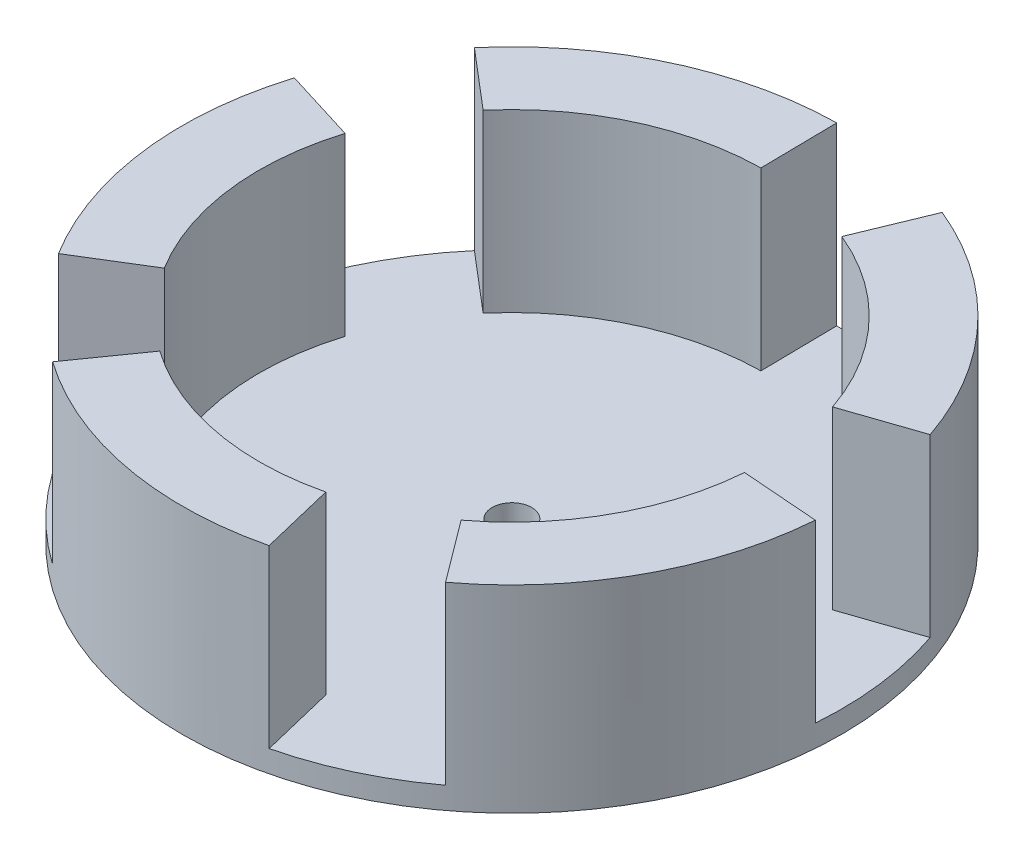
SolidWorks part; units mm, degrees
ref_plane "Front Plane" through (0, 0, 0) normal (0, 0, 1) x (1, 0, 0)
ref_plane "Top Plane" through (0, 0, 0) normal (0, 1, 0) x (1, 0, 0)
ref_plane "Right Plane" through (0, 0, 0) normal (1, 0, 0) x (0, 0, -1)
sketch "Sketch3" plane through (0, 0, 0) normal (0, 1, 0) x (1, 0, 0)
  circle A0 centre (0, 0) radius 30
  dimension "D2" = 60
extrude "Boss-Extrude3" add sketch "Sketch3" along normal blind 2
sketch "Sketch4" plane through (0, 2, 0) normal (0, 1, 0) x (1, 0, 0)
  line L0 (0, 0) -> (-17.5189, 14.9027) construction
  line L1 (0, 0) -> (8.7596, 21.2666) construction
  line L2 (0, 0) -> (21.7702, 7.4201) construction
  line L3 (0, 0) -> (22.9326, -1.7592) construction
  line L4 (0, 0) -> (13.7843, -18.4118) construction
  line L5 (0, 0) -> (5.4135, -22.3538) construction
  line L6 (0, 0) -> (-13.251, -18.7992) construction
  line L7 (0, 0) -> (-19.5869, -12.0563) construction
  line L8 (0, 0) -> (-21.9739, 6.7932) construction
  line L9 (0, 0) -> (-0.3296, 22.9976) construction
  line L10 (-17.5189, 14.9027) -> (-0.3296, 22.9976) construction
  line L11 (-0.3296, 22.9976) -> (8.7596, 21.2666) construction
  line L12 (8.7596, 21.2666) -> (21.7702, 7.4201) construction
  line L13 (21.7702, 7.4201) -> (22.9326, -1.7592) construction
  line L14 (22.9326, -1.7592) -> (13.7843, -18.4118) construction
  line L15 (13.7843, -18.4118) -> (5.4135, -22.3538) construction
  line L16 (5.4135, -22.3538) -> (-13.251, -18.7992) construction
  line L17 (-13.251, -18.7992) -> (-19.5869, -12.0563) construction
  line L18 (-19.5869, -12.0563) -> (-21.9739, 6.7932) construction
  line L19 (-21.9739, 6.7932) -> (-17.5189, 14.9027) construction
  line L20 (13.7843, -18.4118) -> (17.9795, -24.0153)
  line L21 (22.9326, -1.7592) -> (29.9121, -2.2946)
  line L22 (21.7702, 7.4201) -> (28.3959, 9.6784)
  line L23 (8.7596, 21.2666) -> (11.4256, 27.7391)
  line L24 (-0.3296, 22.9976) -> (-0.4299, 29.9969)
  line L25 (-17.5189, 14.9027) -> (-22.8507, 19.4383)
  line L26 (-21.9739, 6.7932) -> (-28.6616, 8.8607)
  line L27 (-19.5869, -12.0563) -> (-25.5481, -15.7255)
  line L28 (-13.251, -18.7992) -> (-17.284, -24.5207)
  line L29 (5.4135, -22.3538) -> (7.0611, -29.1572)
  circle A0 centre (0, 0) radius 23 construction
  arc A1 (-17.5189, 14.9027) -> (-0.3296, 22.9976) centre (0, 0) cw
  arc A2 (8.7596, 21.2666) -> (21.7702, 7.4201) centre (0, 0) cw
  arc A3 (22.9326, -1.7592) -> (13.7843, -18.4118) centre (0, 0) cw
  arc A4 (-13.251, -18.7992) -> (5.4135, -22.3538) centre (0, 0) ccw
  arc A5 (-19.5869, -12.0563) -> (-21.9739, 6.7932) centre (0, 0) cw
  arc A6 (-0.4299, 29.9969) -> (-22.8507, 19.4383) centre (0, 0) ccw
  arc A7 (-28.6616, 8.8607) -> (-25.5481, -15.7255) centre (0, 0) ccw
  arc A8 (7.0611, -29.1572) -> (-17.284, -24.5207) centre (0, 0) cw
  arc A9 (11.4256, 27.7391) -> (28.3959, 9.6784) centre (0, 0) cw
  arc A10 (29.9121, -2.2946) -> (17.9795, -24.0153) centre (0, 0) cw
  circle A11 centre (0, 0) radius 30 construction
  dimension "D1" = 46
  dimension "D2" = 19
extrude "Boss-Extrude4" add sketch "Sketch4" along normal blind 16
sketch "Sketch5" plane through (0, 0, 0) normal (0, -1, 0) x (1, 0, 0)
  line L7 (7.3472, -0.7952) -> (4.3623, 5.9652)
  line L8 (4.3623, 5.9652) -> (-2.9849, 6.7604)
  line L9 (-2.9849, 6.7604) -> (-7.3472, 0.7952)
  line L10 (-7.3472, 0.7952) -> (-4.3623, -5.9652)
  line L11 (-4.3623, -5.9652) -> (2.9849, -6.7604)
  line L12 (2.9849, -6.7604) -> (7.3472, -0.7952)
  circle A7 centre (0, 0) radius 6.4 construction
  circle A8 centre (0, 0) radius 8.5
  dimension "D1" = 12.8
  dimension "D2" = 17
extrude "Boss-Extrude5" add sketch "Sketch5" along normal blind 8
sketch "Sketch6" plane through (0, 0, 0) normal (0, -1, 0) x (1, 0, 0)
  circle A0 centre (0, 0) radius 1.8
  dimension "D1" = 3.6
extrude "Cut-Extrude1" cut sketch "Sketch6" against normal blind 5
fillet "Fillet1" radius 2 1 edges at (0, 0, 8.5)
